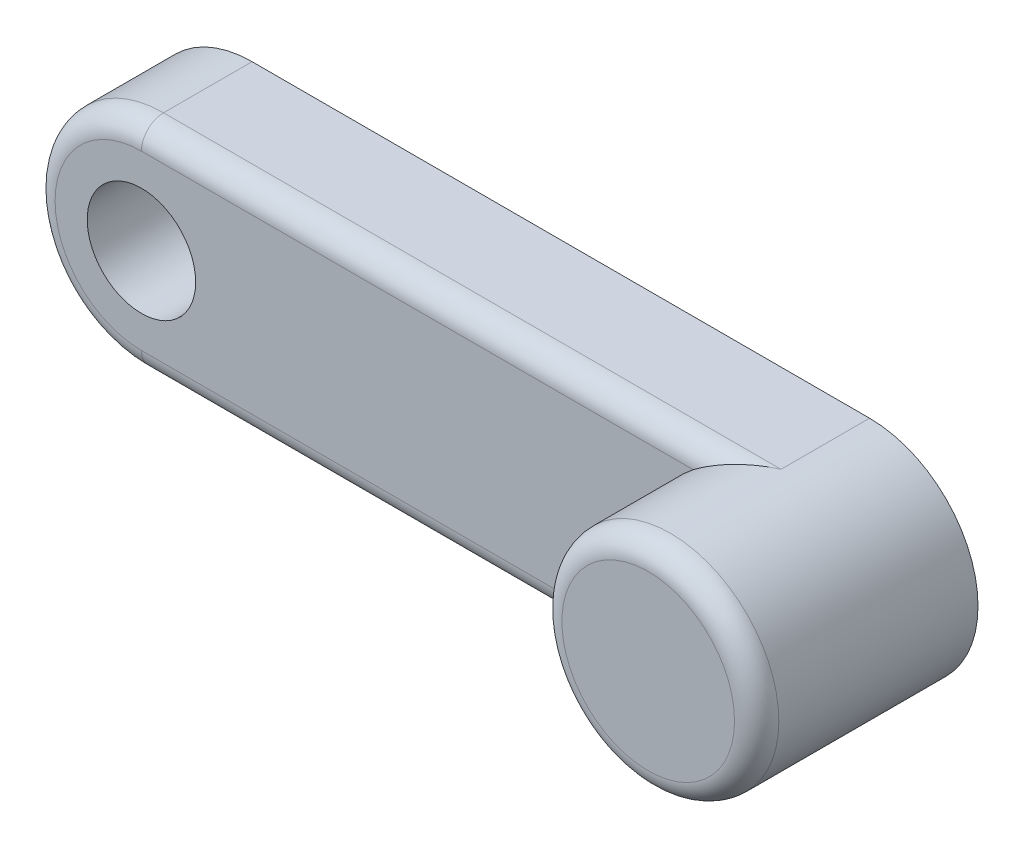
SolidWorks part; units mm, degrees
ref_plane "Front Plane" through (0, 0, 0) normal (0, 0, 1) x (1, 0, 0)
ref_plane "Top Plane" through (0, 0, 0) normal (0, 1, 0) x (1, 0, 0)
ref_plane "Right Plane" through (0, 0, 0) normal (1, 0, 0) x (0, 0, -1)
sketch "Sketch1" plane through (0, 0, 0) normal (0, 0, 1) x (1, 0, 0)
  line L0 (0, 4.9) -> (27.8991, 4.9)
  line L1 (0, -4.9) -> (27.8991, -4.9)
  arc A0 (0, 4.9) -> (0, -4.9) centre (0, 0) ccw
  circle A1 centre (0, 0) radius 2.45
  arc A2 (27.8991, -4.9) -> (27.8991, 4.9) centre (27.8991, 0) ccw
extrude "Boss-Extrude1" add sketch "Sketch1" along normal blind 5
sketch "Sketch2" plane through (0, 0, 0) normal (0, 0, 1) x (1, 0, 0)
  circle A0 centre (27.8991, 0) radius 4.9
extrude "Boss-Extrude2" add sketch "Sketch2" along normal blind 5 from surface starting at face at (13.9496, 0, 5)
fillet "Fillet1" radius 1 4 edges at (13.9496, 4.9, 5) (13.9496, -4.9, 5) (-4.9, 0, 5) (32.7991, 0, 10)
